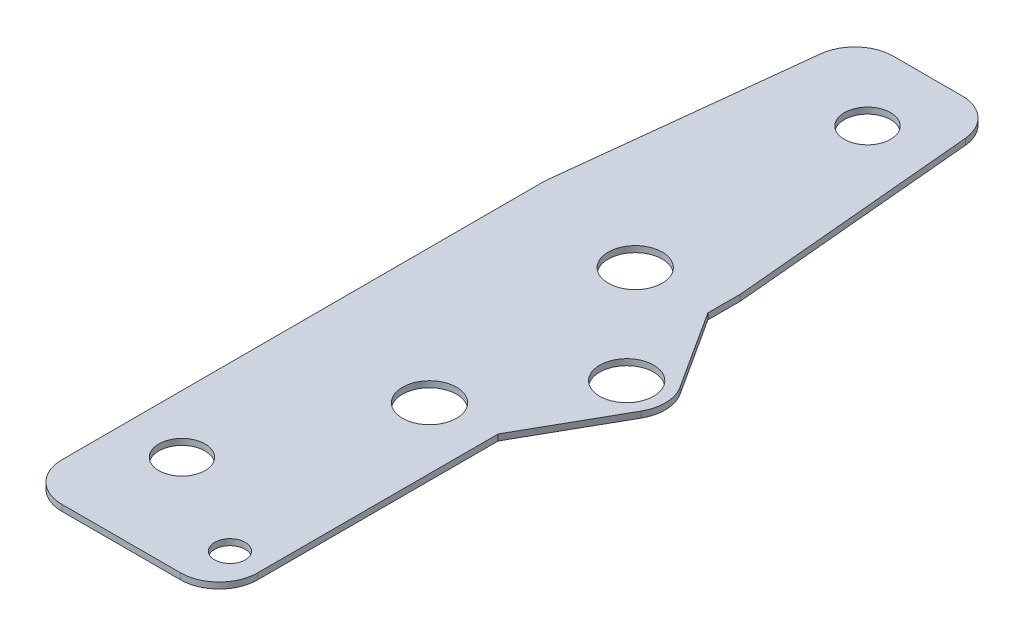
SolidWorks part; units mm, degrees
ref_plane "Front" through (0, 0, 0) normal (0, 0, 1) x (1, 0, 0)
ref_plane "Top" through (0, 0, 0) normal (0, 1, 0) x (1, 0, 0)
ref_plane "Right" through (0, 0, 0) normal (1, 0, 0) x (0, 0, -1)
sketch "Sketch1" plane through (0, 0, 0) normal (0, 1, 0) x (1, 0, 0)
  line L0 (10.4543, 228.6) -> (0, 135.3627)
  line L1 (0, 0) -> (50.8, 0)
  line L2 (0, 0) -> (0, 228.6)
  line L3 (0, 228.6) -> (50.8, 228.6)
  line L4 (50.8, 0) -> (50.8, 228.6)
  line L5 (42.3273, 228.6) -> (50.8, 135.3627)
  line L8 (50.8, 0) -> (24.327, 0)
  line L9 (50.8, 0) -> (50.8, -15)
  line L10 (50.8, -15) -> (24.327, -15)
  line L11 (24.327, 0) -> (24.327, -15)
  line L16 (50.8, 120.6192) -> (50.8, 104.4882)
  line L18 (50.8, 64.8791) -> (50.8, 87.4235)
  circle A0 centre (29.5042, 189.5572) radius 6
  circle A2 centre (24.327, 25.5092) radius 5.969
  circle A3 centre (42.3273, 11.2956) radius 3.9601
  circle A8 centre (31.2038, 127.5833) radius 7
  circle A9 centre (55.4873, 101.061) radius 10
  circle A11 centre (34.8741, 70.5327) radius 7
  dimension "D3" = 12
  dimension "D4" = 11.938
  dimension "D5" = 15
  dimension "D6" = 14
  dimension "D1" = 50.8
  dimension "D2" = 228.6
extrude "Boss-Extrude1" add sketch "Sketch1" along normal blind 1.5875 contours L1 L4 L3 L0 L2 region at (25.0708, 0, -108.2146)
sketch "Sketch4" plane through (0, 0, -228.6) normal (0, 0, -1) x (-1, 0, 0)
  line L1 (-61.3109, 11.9192) -> (4.9615, 11.9192)
  line L2 (-61.3109, 11.9192) -> (-61.3109, -15.8811)
  line L3 (-61.3109, -15.8811) -> (4.9615, -15.8811)
  line L4 (4.9615, 11.9192) -> (4.9615, -15.8811)
extrude "Cut-Extrude2" cut sketch "Sketch4" against normal blind 20
sketch "Sketch5" plane through (0, 0, 0) normal (0, -1, 0) x (1, 0, 0)
  circle A0 centre (24.327, -25.5092) radius 6.6837
extrude "Boss-Extrude2" add sketch "Sketch5" against normal blind 1.5875
sketch "Sketch6" plane through (0, 0, 0) normal (0, -1, 0) x (1, 0, 0)
  line L0 (0, 0) -> (0, -135.3627) construction
  circle A0 centre (15, -26.1497) radius 6
  circle A1 centre (29.5042, -189.5572) radius 6 construction
  dimension "D1" = 164.05
  dimension "D2" = 12
  dimension "D3" = 15
extrude "Cut-Extrude3" cut sketch "Sketch6" against normal blind 2
fillet "Fillet3" radius 10 1 edges at (44.1447, 0.7937, -208.6)
fillet "Fillet4" radius 10 3 edges at (50.8, 0.7937, 0) (0, 0.7937, 0) (8.2118, 0.7937, -208.6)
sketch "Sketch13" plane through (0, 1.5875, 0) normal (0, 1, 0) x (1, 0, 0)
  line L0 (63.9106, 106.4877) -> (50.8, 126.8377)
  line L1 (50.8, 109.8944) -> (50.8, 135.3627) construction
  line L2 (50.8, 126.8377) -> (50.8, 111.0724)
  line L3 (50.8, 111.0724) -> (50.8, 109.8944)
  line L4 (64.2084, 96.1269) -> (50.8, 72.4276)
  line L5 (50.8, 10) -> (50.8, 92.2276) construction
  line L6 (50.8, 72.4276) -> (50.8, 92.2276)
  circle A0 centre (55.4873, 101.061) radius 10.0201
  line M8 (50.8, 10) -> (50.8, 92.2276)
  arc M9 (50.8, 92.2276) -> (50.8, 109.8944) centre (55.4873, 101.061) cw
  line M10 (50.8, 109.8944) -> (50.8, 135.3627)
extrude "Boss-Extrude6" add sketch "Sketch13" against normal blind 1.5875 contours A0 M9 | A0 L0 M10 | A0 L4 M8 region at (54.4725, 1.5875, -115.8856) region at (55.4986, 1.5875, -101.061) region at (54.6074, 1.5875, -85.3296)
sketch "Sketch15" plane through (0, 1.5875, 0) normal (0, 1, 0) x (1, 0, 0)
  circle A0 centre (55.5038, 101.0724) radius 7
extrude "Cut-Extrude5" cut sketch "Sketch15" against normal blind 1.5875
equation "\"7i\"=101.6"
